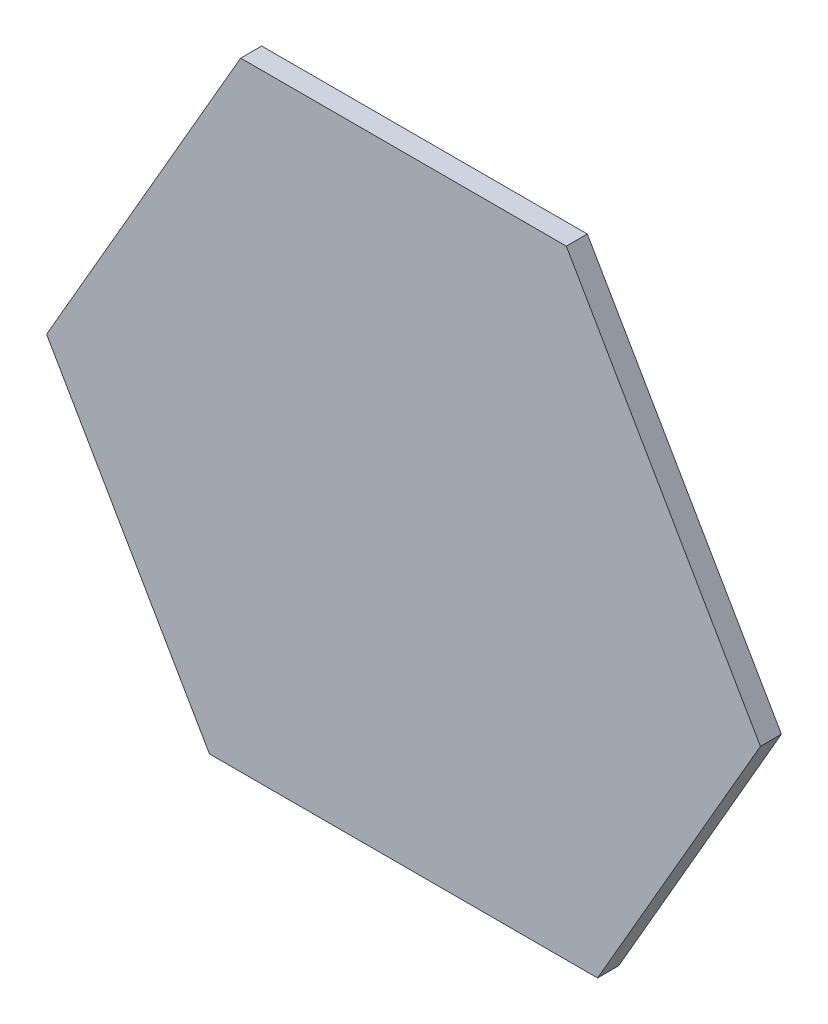
SolidWorks part; units mm, degrees
material "6061-T6 (SS)"
ref_plane "Front" through (0, 0, 0) normal (0, 0, 1) x (1, 0, 0)
ref_plane "Top" through (0, 0, 0) normal (0, 1, 0) x (1, 0, 0)
ref_plane "Right" through (0, 0, 0) normal (1, 0, 0) x (0, 0, -1)
sketch "Sketch1" plane through (0, 0, 0) normal (0, 0, 1) x (1, 0, 0)
  line L0 (-49.2125, 96.1462) -> (49.2125, 96.1462)
  line L1 (-107.8713, -5.4538) -> (0, 0) construction
  line L2 (-49.2125, 96.1462) -> (0, 0) construction
  line L3 (49.2125, 96.1462) -> (107.8713, -5.4538)
  line L4 (107.8713, -5.4538) -> (-107.8713, -5.4538) construction
  line L5 (107.8713, -5.4538) -> (58.6588, -90.6924)
  line L6 (58.6588, -90.6924) -> (-58.6588, -90.6924)
  line L7 (-58.6588, -90.6924) -> (-107.8713, -5.4538)
  line L8 (-107.8713, -5.4538) -> (-49.2125, 96.1462)
  line L9 (0, 0) -> (49.2125, 96.1462) construction
  line L10 (0, 0) -> (107.8713, -5.4538) construction
  line L11 (0, 0) -> (58.6588, -90.6924) construction
  line L13 (0, 0) -> (-58.6588, -90.6924) construction
  dimension "D1" = 98.425
  dimension "D2" = 101.6
extrude "Boss-Extrude1" add sketch "Sketch1" along normal blind 6.35
ref_axis "Axis1" through (0, 0, 0) along (0, 0, 1)
